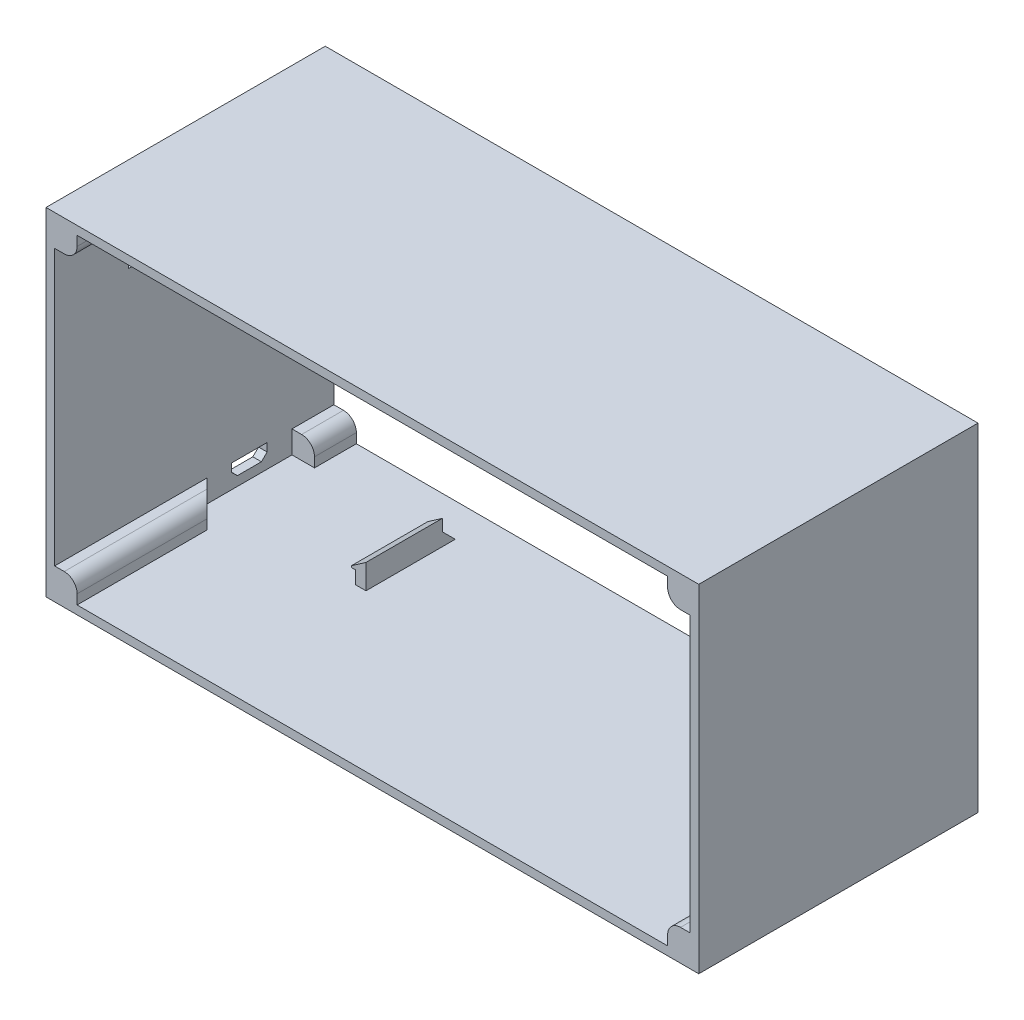
SolidWorks part; units mm, degrees
ref_plane "Plan de face" through (0, 0, 0) normal (0, 0, 1) x (1, 0, 0)
ref_plane "Plan de dessus" through (0, 0, 0) normal (0, 1, 0) x (1, 0, 0)
ref_plane "Plan de droite" through (0, 0, 0) normal (1, 0, 0) x (0, 0, -1)
sketch "Esquisse1" plane through (0, 0, -2.2) normal (0, 0, -1) x (-1, 0, 0)
  line L1 (-32.1075, 39.9055) -> (119.8323, 39.9055)
  line L2 (-32.1075, 39.9055) -> (-32.1075, -38.6114)
  line L3 (-32.1075, -38.6114) -> (119.8323, -38.6114)
  line L4 (119.8323, 39.9055) -> (119.8323, -38.6114)
  line L5 (117.8323, 32.6629) -> (117.8323, -31.3687)
  line L6 (-24.8649, -36.6114) -> (112.5896, -36.6114)
  line L8 (-24.8649, 35.6629) -> (-24.8649, 37.9055)
  line L10 (-27.8649, 32.6629) -> (-30.1075, 32.6629)
  line L12 (-24.8649, 37.9055) -> (112.5896, 37.9055)
  line L13 (-30.1075, 32.6629) -> (-30.1075, -31.3687)
  line L14 (-30.1075, 37.9055) -> (117.8323, 37.9055) construction
  line L15 (112.5896, 37.9055) -> (112.5896, 35.6629)
  line L16 (-30.1075, 37.9055) -> (-30.1075, -36.6114) construction
  line L18 (115.5896, 32.6629) -> (117.8323, 32.6629)
  line L20 (115.5896, -31.3687) -> (117.8323, -31.3687)
  line L21 (117.8323, 37.9055) -> (117.8323, -36.6114) construction
  line L23 (112.5896, -34.3687) -> (112.5896, -36.6114)
  line L24 (-27.8649, -31.3687) -> (-30.1075, -31.3687)
  line L25 (-30.1075, -36.6114) -> (117.8323, -36.6114) construction
  line L27 (-24.8649, -34.3687) -> (-24.8649, -36.6114)
  arc A1 (-27.8649, 32.6629) -> (-24.8649, 35.6629) centre (-27.8649, 35.6629) ccw
  arc A2 (-24.8649, -34.3687) -> (-27.8649, -31.3687) centre (-27.8649, -34.3687) ccw
  arc A3 (115.5896, -31.3687) -> (112.5896, -34.3687) centre (115.5896, -34.3687) ccw
  arc A4 (112.5896, 35.6629) -> (115.5896, 32.6629) centre (115.5896, 35.6629) ccw
  dimension "D1" = 2
extrude "Boss.-Extru.1" add sketch "Esquisse1" along normal blind 65
sketch "Esquisse2" plane through (0, 0, -67.2) normal (0, 0, -1) x (-1, 0, 0)
  line L1 (119.8323, 39.9055) -> (-32.1075, 39.9055)
  line L2 (119.8323, 39.9055) -> (119.8323, -38.6114)
  line L3 (119.8323, -38.6114) -> (-32.1075, -38.6114)
  line L4 (-32.1075, 39.9055) -> (-32.1075, -38.6114)
sketch "Esquisse5" plane through (0, 37.9055, 0) normal (0, -1, 0) x (1, 0, 0)
  circle A0 centre (-16.7337, -61.521) radius 2.8063
  circle A1 centre (-99.3599, -61.521) radius 2.553
  circle A2 centre (-99.3599, -13.1848) radius 2.661
extrude "Boss.-Extru.3" add sketch "Esquisse5" along normal up to surface (5 mm away)
sketch "Esquisse6" plane through (-119.8323, 0, 0) normal (-1, 0, 0) x (0, 0, 1)
  line L0 (-19.9158, 20.4595) -> (-31.8538, 20.4595) construction
  line L1 (-19.4158, 19.9595) -> (-32.3538, 19.9595)
  line L2 (-19.4158, 19.9595) -> (-19.4158, 31.7545)
  line L3 (-19.4158, 31.7545) -> (-32.3538, 31.7545)
  line L4 (-32.3538, 19.9595) -> (-32.3538, 31.7545)
  line L5 (-19.9158, 20.4595) -> (-19.9158, 31.2545) construction
  line L6 (-31.8538, 20.4595) -> (-31.8538, 31.2545) construction
  line L8 (-51.6774, -31.2125) -> (-43.4099, -31.2125)
  line L9 (-51.6774, -31.2125) -> (-51.6774, -33.1364)
  line L10 (-50.3361, -34.4338) -> (-44.7512, -34.4338)
  line L11 (-43.4099, -31.2125) -> (-43.4099, -33.1364)
  line L12 (-51.6774, -33.1364) -> (-50.3361, -34.4338)
  line L13 (-51.7764, -33.1364) -> (-50.9764, -33.1364) construction
  line L14 (-47.5436, -31.2125) -> (-47.5436, -34.4338) construction
  line L15 (-43.4099, -33.1364) -> (-44.7512, -34.4338)
  dimension "D1" = 0.5
  dimension "D2" = 0.5
  dimension "D3" = 0.5
  dimension "D4" = 0.5
extrude "Enlèv. mat.-Extru.1" cut sketch "Esquisse6" against normal blind 2
sketch "Esquisse7" plane through (0, -36.6114, 0) normal (0, 1, 0) x (1, 0, 0)
  line L2 (-117.8323, 57.4564) -> (-117.8323, 37.6764)
  line L6 (-117.8323, 37.6764) -> (-111.5896, 37.6764)
  line L7 (-111.5896, 57.4564) -> (-111.5896, 37.6764)
  line L8 (-117.8323, 57.4564) -> (-111.5896, 57.4564)
  line L10 (-118.8323, 57.4564) -> (-118.8323, 37.6764) construction
  line L11 (-117.8323, 38.6764) -> (-112.5896, 38.6764) construction
  line L12 (-112.5896, 56.4564) -> (-112.5896, 38.6764) construction
  line L13 (-117.8323, 56.4564) -> (-112.5896, 56.4564) construction
  line L14 (-117.8323, 56.4564) -> (-117.8323, 38.6764) construction
  line L16 (-118.8323, 37.6764) -> (-111.5896, 37.6764) construction
  line L17 (-118.8323, 57.4564) -> (-111.5896, 57.4564) construction
  dimension "D1" = 1
extrude "Enlèv. mat.-Extru.2" cut sketch "Esquisse7" along normal up to surface (5.2426 mm away) up to face at (-117.0847, -31.3687, -38.9812)
fillet "Congé1" radius 3 3 edges at (-99.3599, 37.9055, -15.8458) (-99.3599, 37.9055, -64.074) (-16.7337, 37.9055, -64.3273)
sketch "Esquisse8" plane through (0, -36.6114, 0) normal (0, 1, 0) x (1, 0, 0)
  line L0 (-84.8123, 38.6764) -> (-84.8123, 56.4564) construction
  line L1 (-84.3123, 56.4564) -> (-81.8249, 56.4564)
  line L2 (-84.3123, 56.4564) -> (-84.3123, 38.6764)
  line L3 (-84.3123, 38.6764) -> (-81.8249, 38.6764)
  line L4 (-81.8249, 56.4564) -> (-81.8249, 38.6764)
  line L5 (-84.8123, 56.4564) -> (-117.8323, 56.4564) construction
  line L6 (-117.8323, 38.6764) -> (-84.8123, 38.6764) construction
  dimension "D1" = 0.5
extrude "Boss.-Extru.4" add sketch "Esquisse8" along normal blind 3
sketch "Esquisse9" plane through (0, 0, -56.4564) normal (0, 0, -1) x (-1, 0, 0)
  line L0 (81.8249, -33.6114) -> (85.2271, -33.6114)
  line L1 (85.2271, -33.6114) -> (85.2271, -33.2586)
  line L2 (85.2271, -33.2586) -> (81.8249, -30.8882)
  line L3 (81.8249, -30.8882) -> (81.8249, -33.6114)
extrude "Boss.-Extru.5" add sketch "Esquisse9" against normal up to surface (17.78 mm away) up to face at (-83.0686, -35.1114, -38.6764)
chamfer "Chanfrein1" distance 3 angle 45 1 edges at (-83.0686, -36.6114, -56.4564)
sketch "Esquisse10" plane through (0, -36.6114, 0) normal (0, 1, 0) x (1, 0, 0)
  line L0 (-117.8323, 37.6764) -> (-112.5896, 32.4338)
  line L1 (-112.5896, 67.2) -> (-112.5896, 2.2) construction
  line L5 (-112.5896, 32.4338) -> (-112.5896, 37.6764)
  line L6 (-112.5896, 37.6764) -> (-117.8323, 37.6764)
  dimension "D1" = 45
extrude "Enlèv. mat.-Extru.5" cut sketch "Esquisse10" along normal up to surface (5.2426 mm away) up to face at (-116.711, -31.3687, -19.9382)
